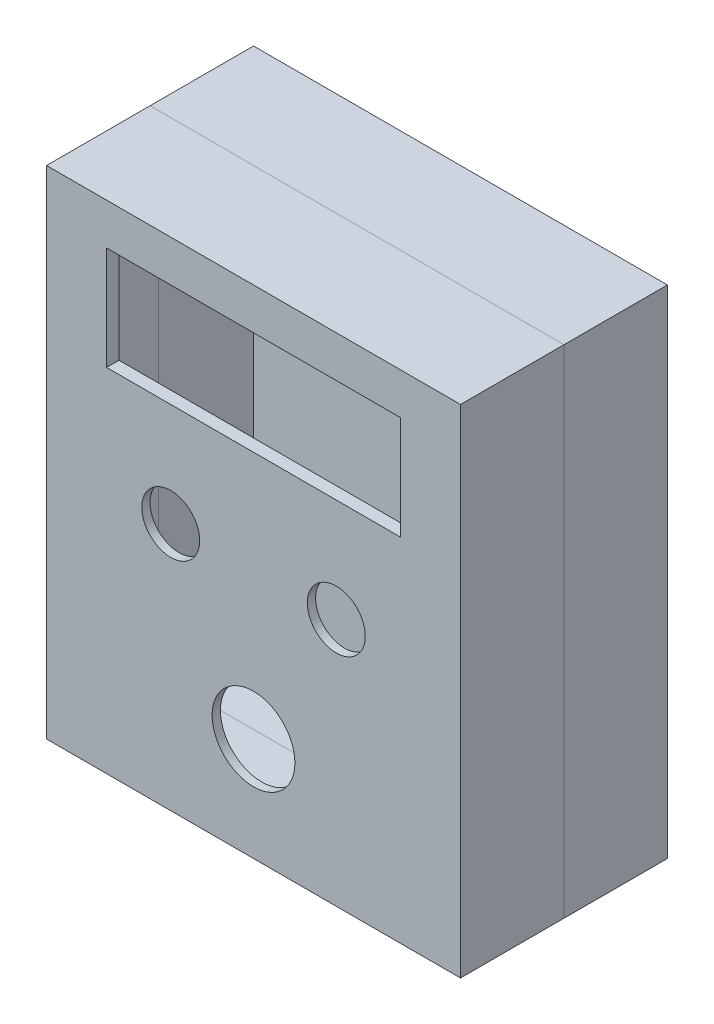
SolidWorks part; units mm, degrees
ref_plane "Front Plane" through (0, 0, 0) normal (0, 0, 1) x (1, 0, 0)
ref_plane "Top Plane" through (0, 0, 0) normal (0, 1, 0) x (1, 0, 0)
ref_plane "Right Plane" through (0, 0, 0) normal (1, 0, 0) x (0, 0, -1)
sketch "Sketch1" plane through (0, 0, 0) normal (1, 0, 0) x (0, 0, -1)
  line L1 (-25, -60) -> (25, -60)
  line L2 (-25, -60) -> (-25, 60)
  line L3 (-25, 60) -> (25, 60)
  line L4 (25, -60) -> (25, 60)
  line L5 (-25, -60) -> (25, 60) construction
  line L6 (-25, 60) -> (25, -60) construction
  point P0 (0, 0)
  dimension "D1" = 50
  dimension "D2" = 120
extrude "Boss-Extrude1" add sketch "Sketch1" along normal blind 100
sketch "Sketch2" plane through (0, 0, 25) normal (0, 0, 1) x (1, 0, 0)
  line L0 (90, 60) -> (90, -60) construction
  line L1 (100, 60) -> (0, 60) construction
  line L2 (100, -60) -> (0, -60) construction
  line L3 (100, 60) -> (100, -60) construction
  line L4 (50, 60) -> (50, -60) construction
  line L6 (14.5, 25) -> (85.5, 25)
  line L7 (14.5, 25) -> (14.5, 50)
  line L8 (14.5, 50) -> (85.5, 50)
  line L9 (85.5, 25) -> (85.5, 50)
  line L10 (14.5, 25) -> (85.5, 50) construction
  line L11 (14.5, 50) -> (85.5, 25) construction
  point P10 (50, 37.5)
  point P15 (50, 39.8006)
  dimension "D1" = 10
  dimension "D2" = 25
  dimension "D3" = 10
  dimension "D4" = 71
extrude "Cut-Extrude1" cut sketch "Sketch2" against normal blind 3
shell "Shell1" thickness 2 removed face at (50, 37.5, 22)
sketch "Sketch3" plane through (0, -60, 0) normal (0, -1, 0) x (1, 0, 0)
  line L0 (50, 25) -> (50, -25) construction
  line L1 (100, 25) -> (0, 25) construction
  line L2 (100, -25) -> (0, -25) construction
  line L4 (10, -11) -> (90, -11)
  line L5 (10, -11) -> (10, -21)
  line L6 (10, -21) -> (90, -21)
  line L7 (90, -11) -> (90, -21)
  line L8 (10, -11) -> (90, -21) construction
  line L9 (10, -21) -> (90, -11) construction
  point P6 (50, -16)
  dimension "D1" = 4
  dimension "D2" = 10
  dimension "D3" = 80
extrude "Cut-Extrude2" cut sketch "Sketch3" against normal blind 3
sketch "Sketch4" plane through (0, 0, 25) normal (0, 0, 1) x (1, 0, 0)
  line L0 (100, -60) -> (0, -60) construction
  circle A0 centre (50, -35) radius 10
  dimension "D1" = 20
  dimension "D2" = 25
extrude "Cut-Extrude3" cut sketch "Sketch4" against normal blind 3
sketch "Sketch5" plane through (0, 0, 25) normal (0, 0, 1) x (1, 0, 0)
  line L0 (0, 0) -> (100, 0) construction
  line L1 (100, 60) -> (100, -60) construction
  line L2 (0, 60) -> (0, -60) construction
  line L3 (50, 60) -> (50, -60) construction
  line L4 (100, 60) -> (0, 60) construction
  line L5 (100, -60) -> (0, -60) construction
  circle A0 centre (30, 0) radius 7
  circle A1 centre (70, 0) radius 7
  dimension "D1" = 14
  dimension "D2" = 30
extrude "Cut-Extrude4" cut sketch "Sketch5" against normal blind 3
split "Split1" trim tools "Front Plane" bodies to split 105 resulting bodies 106 107
